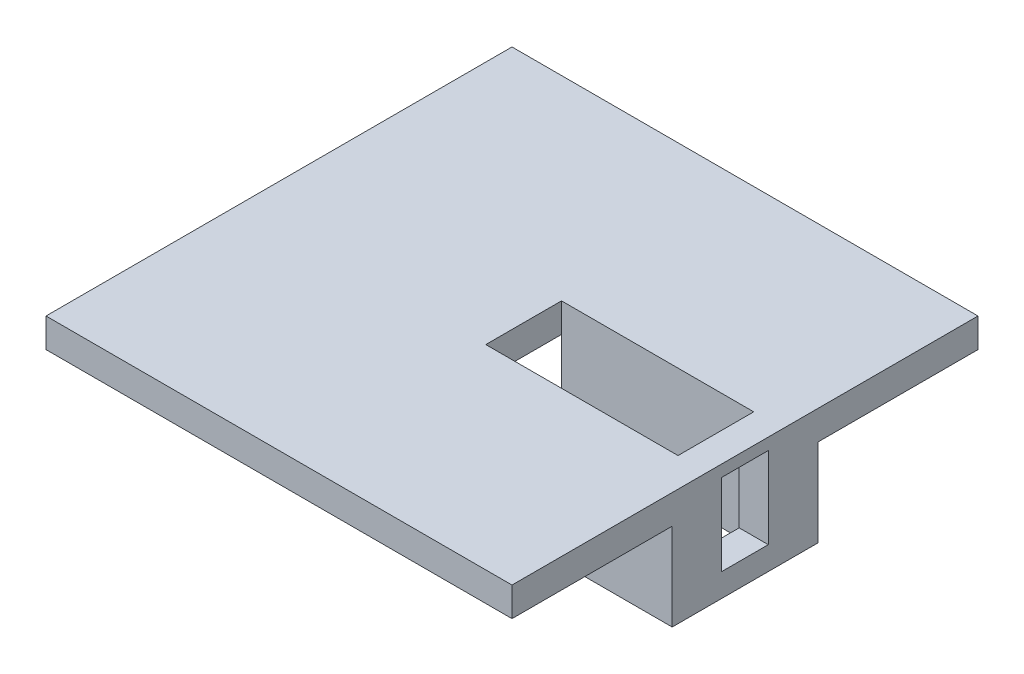
SolidWorks part; units mm, degrees
ref_plane "Front Plane" through (0, 0, 0) normal (0, 0, 1) x (1, 0, 0)
ref_plane "Top Plane" through (0, 0, 0) normal (0, 1, 0) x (1, 0, 0)
ref_plane "Right Plane" through (0, 0, 0) normal (1, 0, 0) x (0, 0, -1)
sketch "Sketch1" plane through (0, 0, 0) normal (0, 1, 0) x (1, 0, 0)
  line L1 (0, 0) -> (80, 0)
  line L2 (0, 0) -> (0, 80)
  line L3 (0, 80) -> (80, 80)
  line L4 (80, 0) -> (80, 80)
  dimension "D1" = 80
  dimension "D2" = 80
extrude "Boss-Extrude1" add sketch "Sketch1" along normal blind 5
sketch "Sketch2" plane through (0, 5, 0) normal (0, 1, 0) x (1, 0, 0)
  line L0 (80, 0) -> (80, 80) construction
  line L1 (42, 46.5) -> (75, 46.5)
  line L2 (42, 46.5) -> (42, 33.5)
  line L3 (42, 33.5) -> (75, 33.5)
  line L4 (75, 46.5) -> (75, 33.5)
  line L5 (0, 40) -> (80, 40) construction
  line L6 (0, 80) -> (0, 0) construction
  line L7 (80, 40) -> (139.4929, 40) construction
  line L8 (139.4929, 40) -> (-53.9504, 40) construction
  dimension "D1" = 33
  dimension "D2" = 13
  dimension "D3" = 5
  dimension "D4" = 6.5
extrude "Cut-Extrude1" cut sketch "Sketch2" against normal through all
sketch "Sketch3" plane through (0, 0, 0) normal (0, -1, 0) x (1, 0, 0)
  line L0 (0, -40) -> (85.8488, -40) construction
  line L1 (42, -46.5) -> (42, -52.5)
  line L2 (42, -52.5) -> (80, -52.5)
  line L3 (80, 0) -> (80, -80) construction
  line L4 (80, -52.5) -> (80, -27.5)
  line L5 (80, -27.5) -> (42, -27.5)
  line L6 (42, -27.5) -> (42, -33.5)
  line L7 (42, -33.5) -> (75, -33.5)
  line L8 (75, -33.5) -> (75, -46.5)
  line L9 (0, -80) -> (0, 0) construction
  line L10 (75, -46.5) -> (42, -46.5)
  dimension "D1" = 6
  dimension "D2" = 6
extrude "Boss-Extrude2" add sketch "Sketch3" along normal blind 15
sketch "Sketch4" plane through (80, 0, 0) normal (1, 0, 0) x (0, 0, -1)
  line L0 (36, 3) -> (44, 3)
  line L1 (44, 3) -> (44, -11)
  line L2 (44, -11) -> (36, -11)
  line L3 (36, -11) -> (36, 3)
  line L5 (0, 5) -> (80, 5) construction
  line L6 (40, 5) -> (40, -15) construction
  line L7 (52.5, -15) -> (27.5, -15) construction
  line L8 (40, -15) -> (40, -31.838) construction
  line L9 (40, -31.838) -> (40, 31.3021) construction
  dimension "D1" = 2
  dimension "D2" = 14
  dimension "D3" = 8
  dimension "D4" = 4
extrude "Cut-Extrude2" cut sketch "Sketch4" against normal up to next
